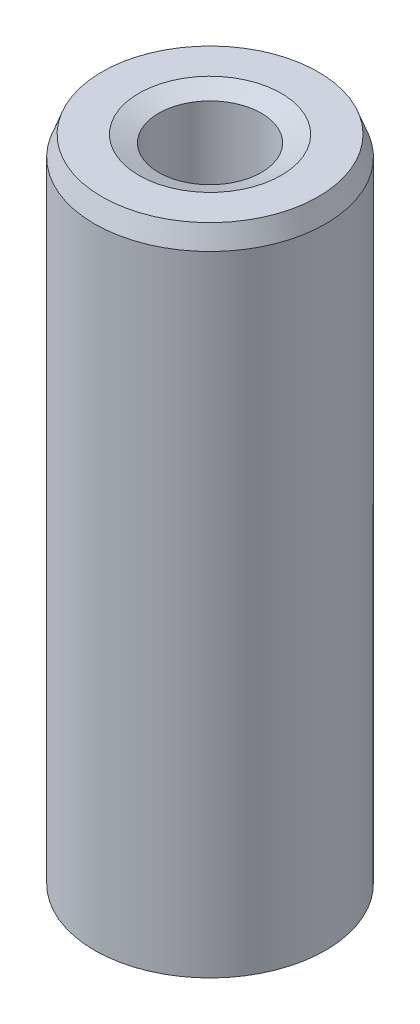
SolidWorks part; units mm, degrees
ref_plane "Front Plane" through (0, 0, 0) normal (0, 0, 1) x (1, 0, 0)
ref_plane "Top Plane" through (0, 0, 0) normal (0, 1, 0) x (1, 0, 0)
ref_plane "Right Plane" through (0, 0, 0) normal (1, 0, 0) x (0, 0, -1)
sketch "Sketch1" plane through (0, 0, 0) normal (0, 1, 0) x (1, 0, 0)
  circle A0 centre (0, 0) radius 7.5
  dimension "SLEEVE_OD" = 15
extrude "Boss-Extrude1" add sketch "Sketch1" along normal blind 42.5999
sketch "Sketch2" plane through (0, 0, 0) normal (0, 1, 0) x (1, 0, 0)
  circle A0 centre (0, 0) radius 3.3338
  dimension "BORE_D" = 6.6675
extrude "Cut-Extrude1" cut sketch "Sketch2" along normal through all
chamfer "Chamfer1" distance 1.2862 angle 20.393 4 edges at (0, 42.5999, 3.3338) (0, 0, 3.3338) (0, 0, 7.5) (0, 42.5999, 7.5) first distance on face at (0, 42.5999, 3.3338) first distance on face at (0, 0, 3.3338) first distance on face at (0, 42.5999, 7.5)
